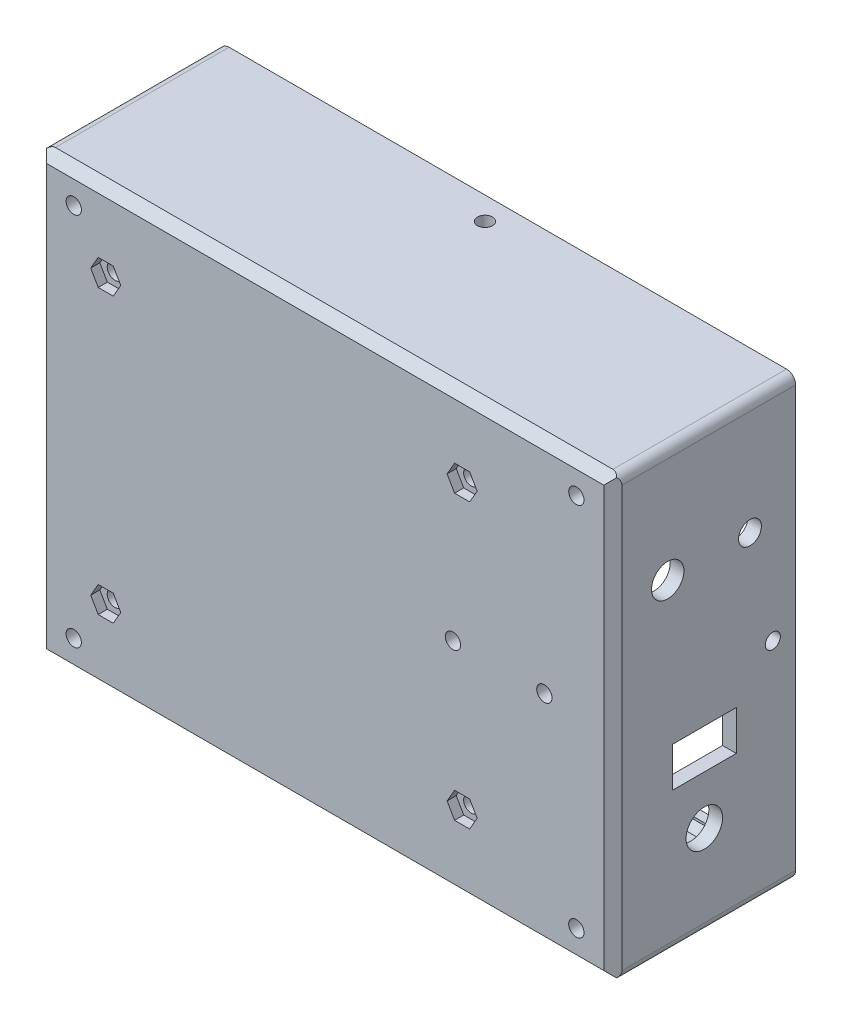
SolidWorks part; units mm, degrees
ref_plane "Front Plane" through (0, 0, 0) normal (0, 0, 1) x (1, 0, 0)
ref_plane "Top Plane" through (0, 0, 0) normal (0, 1, 0) x (1, 0, 0)
ref_plane "Right Plane" through (0, 0, 0) normal (1, 0, 0) x (0, 0, -1)
sketch "Sketch1" plane through (0, 0, 0) normal (0, 0, 1) x (1, 0, 0)
  line L1 (-60, -45) -> (60, -45)
  line L2 (-60, -45) -> (-60, 45)
  line L3 (-60, 45) -> (60, 45)
  line L4 (60, -45) -> (60, 45)
  line L5 (-60, -45) -> (60, 45) construction
  line L6 (-60, 45) -> (60, -45) construction
  line L7 (-48, -31) -> (30, -31)
  line L8 (-48, -31) -> (-48, 31)
  line L9 (-48, 31) -> (30, 31)
  line L10 (30, -31) -> (30, 31)
  line L11 (-48, -31) -> (30, 31) construction
  line L12 (-48, 31) -> (30, -31) construction
  circle A0 centre (-48, 31) radius 1.675
  circle A1 centre (30, 31) radius 1.675
  circle A2 centre (30, -31) radius 1.675
  circle A3 centre (-48, -31) radius 1.675
  circle A4 centre (-55, 41) radius 1.675
  circle A5 centre (55, 41) radius 1.675
  circle A6 centre (55, -41) radius 1.675
  circle A7 centre (-55, -41) radius 1.675
  point P0 (0, 0)
  point P6 (-9, 0)
  dimension "D7" = 3.35
  dimension "D8" = 4
  dimension "D9" = 5
  dimension "D10" = 5
  dimension "D11" = 4
  dimension "D12" = 3.35
  dimension "D13" = 5
  dimension "D14" = 4
  dimension "D15" = 4
  dimension "D16" = 5
  dimension "D1" = 90
  dimension "D2" = 120
  dimension "D3" = 62
  dimension "D4" = 78
  dimension "D5" = 14
  dimension "D6" = 30
extrude "Boss-Extrude2" add sketch "Sketch1" along normal blind 3 contours L1 L4 L3 L2 A3 L8 A0 L9 A1 L10 A2 L7 | A3 L7 A2 L10 A1 L9 A0 L8 region at (-58.5, 0, 0) region at (-9, 0, 0)
sketch "Sketch2" plane through (0, 0, 3) normal (0, 0, 1) x (1, 0, 0)
  line L1 (60, -45) -> (-60, -45)
  line L2 (60, -45) -> (60, 45)
  line L3 (60, 45) -> (-60, 45)
  line L4 (-60, -45) -> (-60, 45)
  line L5 (60, -45) -> (-60, 45) construction
  line L6 (60, 45) -> (-60, -45) construction
  line L7 (63, -48) -> (-63, -48)
  line L8 (63, -48) -> (63, 48)
  line L9 (63, 48) -> (-63, 48)
  line L10 (-63, -48) -> (-63, 48)
  line L11 (63, -48) -> (-63, 48) construction
  line L12 (63, 48) -> (-63, -48) construction
  point P0 (0, 0)
  point P7 (0, 0)
  dimension "D1" = 3
  dimension "D2" = 3
extrude "Boss-Extrude3" add sketch "Sketch2" against normal blind 40
sketch "Sketch4" plane through (63, 0, 0) normal (1, 0, 0) x (0, 0, -1)
  line L0 (37, -48) -> (37, 48) construction
  line L9 (10, -17.35) -> (24, -17.35)
  line L10 (10, -17.35) -> (10, -8.65)
  line L11 (10, -8.65) -> (24, -8.65)
  line L12 (24, -17.35) -> (24, -8.65)
  line L13 (10, -17.35) -> (24, -8.65) construction
  line L14 (10, -8.65) -> (24, -17.35) construction
  line L19 (37, -48) -> (-3, -48) construction
  circle A1 centre (17, -28) radius 4
  point P0 (21, 0)
  point P8 (17, -13)
  dimension "D4" = 8
  dimension "D5" = 8.7
  dimension "D6" = 20
  dimension "D7" = 14
  dimension "D2" = 20
  dimension "D3" = 35
  dimension "D10" = 20
extrude "Cut-Extrude3" cut sketch "Sketch4" against normal blind 10
sketch "Sketch5" plane through (63, 0, 0) normal (1, 0, 0) x (0, 0, -1)
  line L0 (37, -48) -> (37, 48) construction
  line L1 (37, 48) -> (-3, 48) construction
  circle A0 centre (9, 23) radius 3.55
  dimension "D1" = 7.1
  dimension "D2" = 28
  dimension "D3" = 25
extrude "Cut-Extrude4" cut sketch "Sketch5" against normal blind 10
sketch "Sketch6" plane through (63, 0, 0) normal (1, 0, 0) x (0, 0, -1)
  line L0 (37, 48) -> (-3, 48) construction
  line L1 (37, -48) -> (37, 48) construction
  circle A0 centre (27, 23) radius 2.5
  point P3 (27, 23)
  dimension "D5" = 5
  dimension "D2" = 10
  dimension "D1" = 25
extrude "Cut-Extrude5" cut sketch "Sketch6" against normal blind 10 contours A0 | A0 region at (63, 23, -27)
sketch "Sketch8" plane through (0, 0, 0) normal (0, 0, -1) x (-1, 0, 0)
  line L1 (-60, -45) -> (-60, 45) construction
  circle A0 centre (-48, 0) radius 1.675
  circle A1 centre (-28, 0) radius 1.675
  circle A2 centre (-30, 31) radius 1.675 construction
  dimension "D1" = 3.35
  dimension "D2" = 3.35
  dimension "D3" = 20
  dimension "D4" = 31
  dimension "D5" = 31
  dimension "D6" = 12
extrude "Cut-Extrude6" cut sketch "Sketch8" against normal blind 10
sketch "Sketch9" plane through (0, 0, 0) normal (0, 0, -1) x (-1, 0, 0)
  line L0 (60, -45) -> (-60, -45) construction
  line L1 (-46.3834, 2.8) -> (-49.6166, 2.8)
  line L2 (-49.6166, 2.8) -> (-51.2332, 0)
  line L3 (-51.2332, 0) -> (-49.6166, -2.8)
  line L4 (-49.6166, -2.8) -> (-46.3834, -2.8)
  line L5 (-46.3834, -2.8) -> (-44.7668, 0)
  line L6 (-44.7668, 0) -> (-46.3834, 2.8)
  line L7 (-26.3834, 2.8) -> (-29.6166, 2.8)
  line L8 (-29.6166, 2.8) -> (-31.2332, 0)
  line L9 (-31.2332, 0) -> (-29.6166, -2.8)
  line L10 (-29.6166, -2.8) -> (-26.3834, -2.8)
  line L11 (-26.3834, -2.8) -> (-24.7668, 0)
  line L12 (-24.7668, 0) -> (-26.3834, 2.8)
  line L13 (-45.2287, 4.8) -> (-50.7713, 4.8)
  line L14 (-50.7713, 4.8) -> (-53.5426, 0)
  line L15 (-53.5426, 0) -> (-50.7713, -4.8)
  line L16 (-50.7713, -4.8) -> (-45.2287, -4.8)
  line L17 (-45.2287, -4.8) -> (-42.4574, 0)
  line L18 (-42.4574, 0) -> (-45.2287, 4.8)
  line L19 (-25.2287, 4.8) -> (-30.7713, 4.8)
  line L20 (-30.7713, 4.8) -> (-33.5426, 0)
  line L21 (-33.5426, 0) -> (-30.7713, -4.8)
  line L22 (-30.7713, -4.8) -> (-25.2287, -4.8)
  line L23 (-25.2287, -4.8) -> (-22.4574, 0)
  line L24 (-22.4574, 0) -> (-25.2287, 4.8)
  line L25 (60, -45) -> (-60, -45) construction
  line L26 (-51.7668, 41) -> (-53.3834, 43.8)
  line L27 (-53.3834, 43.8) -> (-56.6166, 43.8)
  line L28 (-56.6166, 43.8) -> (-58.2332, 41)
  line L29 (-58.2332, 41) -> (-56.6166, 38.2)
  line L30 (-56.6166, 38.2) -> (-53.3834, 38.2)
  line L31 (-53.3834, 38.2) -> (-51.7668, 41)
  line L32 (-50.6121, 41) -> (-52.8061, 44.8)
  line L33 (-52.8061, 44.8) -> (-57.1939, 44.8)
  line L34 (-57.1939, 44.8) -> (-59.3879, 41)
  line L35 (-59.3879, 41) -> (-57.1939, 37.2)
  line L36 (-57.1939, 37.2) -> (-52.8061, 37.2)
  line L37 (-52.8061, 37.2) -> (-50.6121, 41)
  line L38 (58.2332, 41) -> (56.6166, 43.8)
  line L39 (56.6166, 43.8) -> (53.3834, 43.8)
  line L40 (53.3834, 43.8) -> (51.7668, 41)
  line L41 (51.7668, 41) -> (53.3834, 38.2)
  line L42 (53.3834, 38.2) -> (56.6166, 38.2)
  line L43 (56.6166, 38.2) -> (58.2332, 41)
  line L44 (52.8061, 44.8) -> (50.6121, 41)
  line L45 (50.6121, 41) -> (52.8061, 37.2)
  line L46 (52.8061, 37.2) -> (57.1939, 37.2)
  line L47 (57.1939, 37.2) -> (59.3879, 41)
  line L48 (59.3879, 41) -> (57.1939, 44.8)
  line L49 (57.1939, 44.8) -> (52.8061, 44.8)
  line L50 (53.3834, -38.2) -> (51.7668, -41)
  line L51 (51.7668, -41) -> (53.3834, -43.8)
  line L52 (53.3834, -43.8) -> (56.6166, -43.8)
  line L53 (56.6166, -43.8) -> (58.2332, -41)
  line L54 (58.2332, -41) -> (56.6166, -38.2)
  line L55 (56.6166, -38.2) -> (53.3834, -38.2)
  line L56 (50.6121, -41) -> (52.8061, -44.8)
  line L57 (52.8061, -44.8) -> (57.1939, -44.8)
  line L58 (57.1939, -44.8) -> (59.3879, -41)
  line L59 (59.3879, -41) -> (57.1939, -37.2)
  line L60 (57.1939, -37.2) -> (52.8061, -37.2)
  line L61 (52.8061, -37.2) -> (50.6121, -41)
  line L62 (-53.3834, -38.2) -> (-56.6166, -38.2)
  line L63 (-56.6166, -38.2) -> (-58.2332, -41)
  line L64 (-58.2332, -41) -> (-56.6166, -43.8)
  line L65 (-56.6166, -43.8) -> (-53.3834, -43.8)
  line L66 (-53.3834, -43.8) -> (-51.7668, -41)
  line L67 (-51.7668, -41) -> (-53.3834, -38.2)
  line L68 (-52.8061, -37.2) -> (-57.1939, -37.2)
  line L69 (-57.1939, -37.2) -> (-59.3879, -41)
  line L70 (-59.3879, -41) -> (-57.1939, -44.8)
  line L71 (-57.1939, -44.8) -> (-52.8061, -44.8)
  line L72 (-52.8061, -44.8) -> (-50.6121, -41)
  line L73 (-50.6121, -41) -> (-52.8061, -37.2)
  circle A0 centre (-48, 0) radius 2.8 construction
  circle A1 centre (-28, 0) radius 2.8 construction
  circle A2 centre (-48, 0) radius 4.8 construction
  circle A3 centre (-28, 0) radius 4.8 construction
  circle A4 centre (-55, 41) radius 2.8 construction
  circle A5 centre (-55, 41) radius 3.8 construction
  circle A6 centre (55, 41) radius 2.8 construction
  circle A7 centre (55, 41) radius 3.8 construction
  circle A8 centre (55, -41) radius 2.8 construction
  circle A9 centre (55, -41) radius 3.8 construction
  circle A10 centre (-55, -41) radius 2.8 construction
  circle A11 centre (-55, -41) radius 3.8 construction
  dimension "D1" = 5.6
  dimension "D2" = 2
  dimension "D3" = 5.6
  dimension "D4" = 1
extrude "Boss-Extrude4" add sketch "Sketch9" along normal blind 2
sketch "Sketch10" plane through (0, 0, 3) normal (0, 0, 1) x (1, 0, 0)
  line L0 (63, 48) -> (-63, 48) construction
  line L1 (-44.7091, 31) -> (-46.3546, 33.85)
  line L2 (-46.3546, 33.85) -> (-49.6454, 33.85)
  line L3 (-49.6454, 33.85) -> (-51.2909, 31)
  line L4 (-51.2909, 31) -> (-49.6454, 28.15)
  line L5 (-49.6454, 28.15) -> (-46.3546, 28.15)
  line L6 (-46.3546, 28.15) -> (-44.7091, 31)
  line L7 (33.2909, 31) -> (31.6454, 33.85)
  line L8 (31.6454, 33.85) -> (28.3546, 33.85)
  line L9 (28.3546, 33.85) -> (26.7091, 31)
  line L10 (26.7091, 31) -> (28.3546, 28.15)
  line L11 (28.3546, 28.15) -> (31.6454, 28.15)
  line L12 (31.6454, 28.15) -> (33.2909, 31)
  line L25 (-44.7091, -31) -> (-46.3546, -28.15)
  line L26 (-46.3546, -28.15) -> (-49.6454, -28.15)
  line L27 (-49.6454, -28.15) -> (-51.2909, -31)
  line L28 (-51.2909, -31) -> (-49.6454, -33.85)
  line L29 (-49.6454, -33.85) -> (-46.3546, -33.85)
  line L30 (-46.3546, -33.85) -> (-44.7091, -31)
  line L31 (33.2909, -31) -> (31.6454, -28.15)
  line L32 (31.6454, -28.15) -> (28.3546, -28.15)
  line L33 (28.3546, -28.15) -> (26.7091, -31)
  line L34 (26.7091, -31) -> (28.3546, -33.85)
  line L35 (28.3546, -33.85) -> (31.6454, -33.85)
  line L36 (31.6454, -33.85) -> (33.2909, -31)
  circle A0 centre (-48, 31) radius 2.85 construction
  circle A1 centre (30, 31) radius 2.85 construction
  circle A4 centre (-48, -31) radius 2.85 construction
  circle A5 centre (30, -31) radius 2.85 construction
  dimension "D2" = 5.7
extrude "Cut-Extrude8" cut sketch "Sketch10" against normal blind 2
sketch "Sketch12" plane through (0, 0, 0) normal (0, 0, -1) x (-1, 0, 0)
  circle A0 centre (-30, 31) radius 1.675
  circle A1 centre (48, 31) radius 1.675
  circle A2 centre (48, -31) radius 1.675
  circle A3 centre (-30, -31) radius 1.675
  circle A4 centre (-30, -31) radius 4
  circle A5 centre (48, -31) radius 4
  circle A6 centre (48, 31) radius 4
  circle A7 centre (-30, 31) radius 4
  circle A8 centre (-30, 31) radius 1.675 construction
  circle A9 centre (48, 31) radius 1.675 construction
  circle A10 centre (-30, -31) radius 1.675 construction
  circle A11 centre (48, -31) radius 1.675 construction
  dimension "D1" = 8
extrude "Boss-Extrude11" add sketch "Sketch12" along normal blind 3.5
sketch "Sketch16" plane through (0, 0, 0) normal (0, 0, -1) x (-1, 0, 0)
  line L0 (-50.6121, 43) -> (44, 43)
  line L1 (44, 43) -> (44, 30.25)
  line L2 (47.25, 27) -> (58, 27)
  line L3 (58, 27) -> (58, -27)
  line L4 (58, -27) -> (47.25, -27)
  line L5 (44, -30.25) -> (44, -43)
  line L6 (44, -43) -> (-50.6121, -43)
  line L7 (-50.6121, -43) -> (-50.6121, -37.2)
  line L8 (-50.6121, -37.2) -> (-58, -37.2)
  line L9 (-58, -37.2) -> (-58, 37.2)
  line L10 (-58, 37.2) -> (-50.6121, 37.2)
  line L11 (-50.6121, 37.2) -> (-50.6121, 43)
  line L12 (-58, 4.8) -> (-22.4574, 4.8)
  line L13 (-22.4574, 4.8) -> (-22.4574, -4.8)
  line L14 (-22.4574, -4.8) -> (-58, -4.8)
  line L15 (-22.4574, 1) -> (58, 1)
  line L16 (58, 1) -> (58, -1)
  line L17 (58, -1) -> (-22.4574, -1)
  line L18 (-60, 45) -> (-60, -45)
  line L19 (60, -45) -> (-60, -45) construction
  line L20 (-60, -45) -> (-60, 45) construction
  line L21 (-60, -45) -> (60, -45)
  line L22 (60, -45) -> (60, 45)
  line L23 (60, 45) -> (-60, 45)
  line L24 (-1.5, 43) -> (-1.5, -43)
  line L25 (-1.5, -43) -> (0.5, -43)
  line L26 (0.5, -43) -> (0.5, 43)
  line L27 (0.5, 43) -> (-1.5, 43)
  line L28 (-45.2287, 4.8) -> (-50.7713, 4.8) construction
  line L29 (-50.7713, -4.8) -> (-45.2287, -4.8) construction
  line L30 (-60, -45) -> (-60, 45) construction
  line L31 (-52.8061, -37.2) -> (-57.1939, -37.2) construction
  line L32 (-57.1939, 37.2) -> (-52.8061, 37.2) construction
  line L33 (-50.6121, 41) -> (-52.8061, 37.2)
  line L34 (-52.8061, -37.2) -> (-50.6121, -41)
  line L35 (-22.4574, -1) -> (-24.6514, -4.8)
  line L36 (-24.6514, 4.8) -> (-22.4574, 1)
  line L37 (-22.4574, 0) -> (-25.2287, 4.8) construction
  line L38 (-25.2287, -4.8) -> (-22.4574, 0) construction
  circle A0 centre (48, -31) radius 4 construction
  circle A1 centre (48, 31) radius 4 construction
  arc A2 (47.25, -27) -> (44, -30.25) centre (47.25, -30.25) ccw
  arc A3 (44, 30.25) -> (47.25, 27) centre (47.25, 30.25) ccw
  circle M27 centre (-30, -31) radius 4
  line M34 (-45.2287, -4.8) -> (-50.7713, -4.8)
  line M37 (-50.7713, 4.8) -> (-45.2287, 4.8)
  line M40 (-25.2287, -4.8) -> (-30.7713, -4.8)
  line M43 (-30.7713, 4.8) -> (-25.2287, 4.8)
  line M44 (-50.6121, 41) -> (-52.8061, 37.2)
  line M45 (-52.8061, 37.2) -> (-57.1939, 37.2)
  line M54 (52.8061, 37.2) -> (50.6121, 41)
  line M55 (50.6121, 41) -> (52.8061, 44.8)
  line M56 (50.6121, -41) -> (52.8061, -37.2)
  line M61 (52.8061, -44.8) -> (50.6121, -41)
  line M62 (-52.8061, -37.2) -> (-50.6121, -41)
  line M67 (-57.1939, -37.2) -> (-52.8061, -37.2)
  circle M69 centre (-30, 31) radius 4
  dimension "D9" = 3.25
  dimension "D1" = 2
  dimension "D2" = 2
  dimension "D3" = 2
  dimension "D4" = 1
  dimension "D5" = 1.5
  dimension "D6" = 2
  dimension "D7" = 2
  dimension "D8" = 2
extrude "Cut-Extrude11" cut sketch "Sketch16" against normal blind 2 contours L24 L0 L11 L10 L9 L12 L13 L15 M45 M37 M43 M69 | L26 L15 L3 L2 L1 L0 M54 M55 | L26 L6 L5 L4 L3 L17 M61 M56 | L24 L17 L13 L14 L9 L8 L7 L6 M40 M34 M67 M27 | L7 L8 M62 | L10 L11 M44 | L12 L36 L13 | L13 L35 L14 region at (28.5937, 22.6302, 0) region at (51.3434, 38.4667, 0) region at (-27.0447, 20.6782, 0) region at (23.1887, 3.5333, 0) region at (28.5937, -22.6302, 0) region at (-27.0447, -20.6782, 0) region at (23.1887, -3.5333, 0) region at (51.3434, -38.4667, 0)
sketch "Sketch17" plane through (0, 45, 0) normal (0, -1, 0) x (1, 0, 0)
  line L1 (-58, -35) -> (57, -35)
  line L2 (-58, -35) -> (-58, -2)
  line L3 (-58, -2) -> (57, -2)
  line L4 (57, -35) -> (57, -2)
  line L5 (-60, 0) -> (60, 0) construction
  line L6 (60, -37) -> (60, 0) construction
  line L7 (-60, -37) -> (-60, 0) construction
  line L8 (60, -37) -> (-60, -37) construction
  line L9 (-0.5, 2) -> (-0.5, 0) construction
  line L10 (-58, -17) -> (57, -17)
  line L11 (-58, -17) -> (-58, -19)
  line L12 (-58, -19) -> (57, -19)
  line L13 (57, -17) -> (57, -19)
  line L14 (-0.5, -2) -> (1.5, -2)
  line L15 (-0.5, -2) -> (-0.5, -35)
  line L16 (-0.5, -35) -> (1.5, -35)
  line L17 (1.5, -2) -> (1.5, -35)
  dimension "D1" = 2
  dimension "D2" = 3
  dimension "D3" = 2
  dimension "D4" = 2
  dimension "D5" = 2
  dimension "D6" = 2
  dimension "D7" = 15
extrude "Cut-Extrude13" cut sketch "Sketch17" against normal blind 2 contours L15 L12 L2 L1 | L15 L3 L2 L10 | L3 L17 L10 L4 | L12 L17 L1 L4 region at (-29.25, 45, -27) region at (29.25, 45, -27) region at (-29.25, 45, -9.5) region at (29.25, 45, -9.5)
sketch "Sketch20" plane through (0, -45, 0) normal (0, 1, 0) x (1, 0, 0)
  line L0 (-58, -2) -> (-58, 0) construction
  line L1 (-58, 35) -> (58, 35)
  line L2 (-58, 35) -> (-58, 2)
  line L3 (-58, 2) -> (58, 2)
  line L4 (58, 35) -> (58, 2)
  line L5 (-0.5, 35) -> (1.5, 35)
  line L6 (-0.5, 35) -> (-0.5, 2)
  line L7 (-0.5, 2) -> (1.5, 2)
  line L8 (1.5, 35) -> (1.5, 2)
  line L9 (-58, 19) -> (58, 19)
  line L10 (-58, 19) -> (-58, 17)
  line L11 (-58, 17) -> (58, 17)
  line L12 (58, 19) -> (58, 17)
  line L13 (58, -2) -> (58, 0) construction
  line L15 (-60, 37) -> (60, 37) construction
  line L16 (-58, 19) -> (-0.5, 19) construction
  line L17 (-58, 2) -> (-0.5, 2) construction
  line L18 (1.5, 19) -> (57, 19) construction
  line L20 (-0.5, 2) -> (-0.5, 17) construction
  dimension "D1" = 2
  dimension "D2" = 2
  dimension "D3" = 2
extrude "Cut-Extrude14" cut sketch "Sketch20" against normal blind 2 contours L2 L9 L6 L1 | L8 L9 L4 L1 | L11 L8 L3 L4 | L11 L2 L3 L6 region at (-29.25, -45, -27) region at (29.75, -45, -27) region at (-29.25, -45, -9.5) region at (29.75, -45, -9.5)
sketch "Sketch21" plane through (-60, 0, 0) normal (1, 0, 0) x (0, 0, -1)
  line L0 (0, -45) -> (0, 45) construction
  line L1 (27, 43) -> (2, 43)
  line L2 (27, 43) -> (27, -43)
  line L3 (27, -43) -> (2, -43)
  line L4 (2, 43) -> (2, -43)
  line L5 (27, 37) -> (35, 37)
  line L6 (27, 37) -> (27, -37)
  line L7 (27, -37) -> (35, -37)
  line L8 (35, 37) -> (35, -37)
  line L9 (2, 1) -> (35, 1)
  line L10 (2, 1) -> (2, -1)
  line L11 (2, -1) -> (35, -1)
  line L12 (35, 1) -> (35, -1)
  line L13 (19, 43) -> (17, 43)
  line L14 (19, 43) -> (19, -43)
  line L15 (19, -43) -> (17, -43)
  line L16 (17, 43) -> (17, -43)
  line L17 (37, 45) -> (0, 45) construction
  line L18 (37, 45) -> (37, -45) construction
  line L19 (37, -45) -> (0, -45) construction
  line L20 (-2, -1) -> (0, -1) construction
  dimension "D1" = 2
  dimension "D2" = 2
  dimension "D3" = 2
  dimension "D4" = 2
  dimension "D5" = 6
  dimension "D6" = 6
  dimension "D7" = 8
  dimension "D8" = 2
  dimension "D9" = 2
  dimension "D10" = 15
extrude "Cut-Extrude15" cut sketch "Sketch21" against normal blind 2 contours L2 L9 L8 L5 | L1 L14 L9 L2 | L11 L2 L7 L8 | L11 L14 L3 L2 | L16 L11 L4 L3 | L16 L1 L4 L9 region at (-60, 22, -23) region at (-60, 19, -31) region at (-60, 22, -9.5) region at (-60, -22, -23) region at (-60, -19, -31) region at (-60, -22, -9.5)
chamfer "Chamfer6" distance 1.5 angle 45 14 edges at (29.75, -47, -17) (29.75, -47, -35) (-29.25, -47, -35) (-29.25, -47, -17) (-62, 22, -17) (-62, -22, -17) (-62, 40, -27) (-62, -19, -35) (-62, -40, -27) (-62, 19, -35) (-29.25, 47, -17) (29.25, 47, -17) (-29.25, 47, -35) (29.25, 47, -35)
chamfer "Chamfer7" distance 2 angle 45 4 edges at (-63, 0, 3) (0, 48, 3) (63, 0, 3) (0, -48, 3)
fillet "Fillet1" radius 2 4 edges at (-63, -48, -18) (-63, 48, -18) (63, 48, -18) (63, -48, -18)
sketch "Sketch22" plane through (60, 0, 0) normal (-1, 0, 0) x (0, 0, 1)
  line L1 (-4, 16.95) -> (-14, 16.95)
  line L2 (-4, 16.95) -> (-4, 29.05)
  line L3 (-4, 29.05) -> (-14, 29.05)
  line L4 (-14, 16.95) -> (-14, 29.05)
  line L5 (-4, 16.95) -> (-14, 29.05) construction
  line L6 (-4, 29.05) -> (-14, 16.95) construction
  line L7 (-14, 29.05) -> (-4, 29.05)
  line L8 (-14, 29.05) -> (-14, 31.05)
  line L9 (-14, 31.05) -> (-4, 31.05)
  line L10 (-4, 29.05) -> (-4, 31.05)
  line L11 (-4, 16.95) -> (-14, 16.95)
  line L12 (-4, 16.95) -> (-4, 14.95)
  line L13 (-4, 14.95) -> (-14, 14.95)
  line L14 (-14, 16.95) -> (-14, 14.95)
  point P0 (-9, 23)
  dimension "D1" = 2
  dimension "D2" = 2
  dimension "D3" = 10
  dimension "D4" = 12.1
extrude "Boss-Extrude12" add sketch "Sketch22" along normal blind 2 contours L3 L10 L9 L8 | L1 L14 L13 L12 region at (60, 15.95, -9) region at (60, 30.05, -9)
chamfer "Chamfer8" distance 2 angle 45 2 edges at (58, 30.05, -4) (58, 15.95, -4)
sketch "Sketch23" plane through (0, -48, 0) normal (0, -1, 0) x (1, 0, 0)
  line L0 (-61, -37) -> (61, -37) construction
  line L1 (-63, -37) -> (-63, 1) construction
  circle A0 centre (0, -32) radius 1.65
  dimension "D1" = 5
  dimension "D2" = 3.3
  dimension "D3" = 63
extrude "Cut-Extrude16" cut sketch "Sketch23" against normal up to surface (96 mm away) up to face at (0, 48, -18)
sketch "Sketch24" plane through (63, 0, 0) normal (1, 0, 0) x (0, 0, -1)
  line L0 (-1, 48) -> (37, 48) construction
  line L1 (37, -46) -> (37, 46) construction
  circle A0 centre (32, 0) radius 1.65
  dimension "D1" = 48
  dimension "D2" = 5
  dimension "D3" = 3.3
extrude "Cut-Extrude17" cut sketch "Sketch24" against normal up to surface (126 mm away) up to face at (-63, 0, -18)
sketch "Sketch25" plane through (-62, 0, 0) normal (1, 0, 0) x (0, 0, -1)
  circle A0 centre (32, 0) radius 1.65
  circle A1 centre (32, 0) radius 2.65
  arc A2 (33.3124, 1) -> (30.6876, 1) centre (32, 0) ccw construction
  dimension "D1" = 1
extrude "Boss-Extrude13" add sketch "Sketch25" along normal up to surface (2 mm away) up to face at (-60, -22, -9.5)
sketch "Sketch26" plane through (0, 45, 0) normal (0, -1, 0) x (1, 0, 0)
  circle A0 centre (0, -32) radius 2.65
  circle A1 centre (0, -32) radius 1.65
  arc A2 (-0.5, -30.4276) -> (-0.6874, -33.5) centre (0, -32) ccw construction
  dimension "D1" = 1
extrude "Boss-Extrude14" add sketch "Sketch26" against normal up to surface (2 mm away) up to face at (-23.7481, 47, -27.0727)
sketch "Sketch27" plane through (0, -45, 0) normal (0, 1, 0) x (1, 0, 0)
  circle A0 centre (0, 32) radius 1.65
  circle A1 centre (0, 32) radius 2.65
  arc A2 (1.5, 31.3126) -> (1.5, 32.6874) centre (0, 32) ccw construction
  dimension "D1" = 1
extrude "Boss-Extrude15" add sketch "Sketch27" against normal up to surface (2 mm away) up to face at (20.3583, -47, -28.1667)
